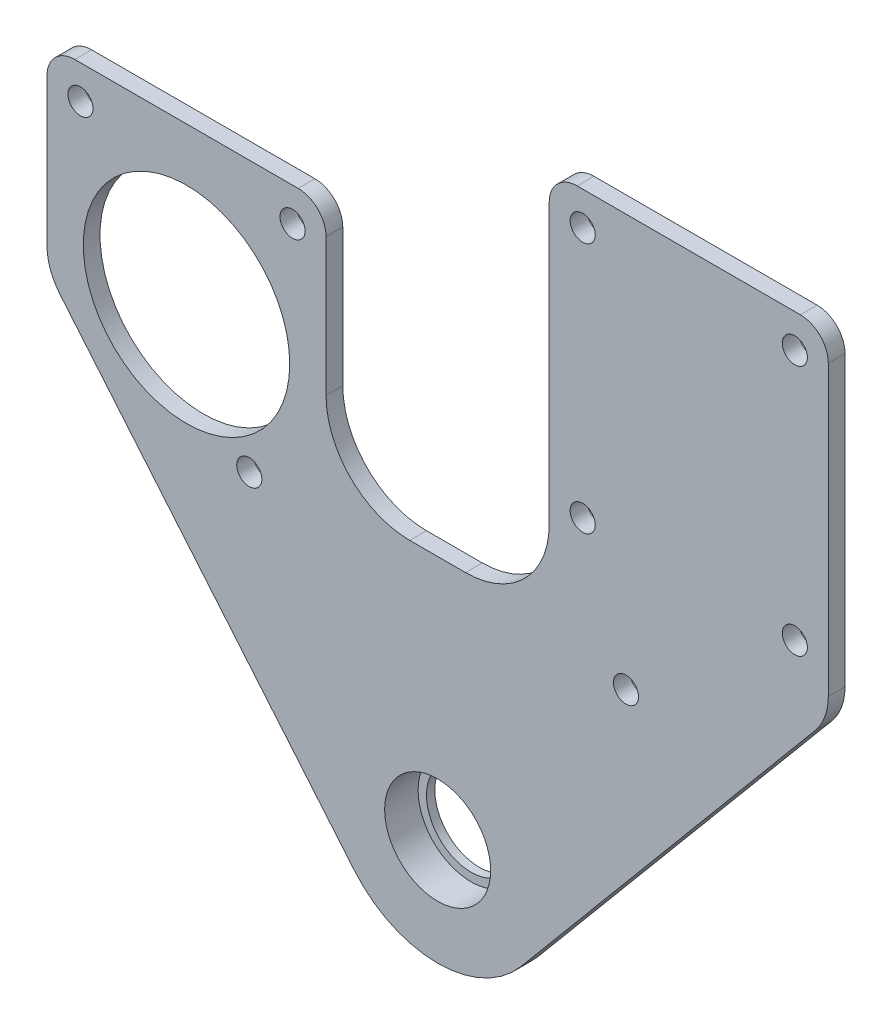
SolidWorks part; units mm, degrees
material "ABS"
ref_plane "Front Plane" through (0, 0, 0) normal (0, 0, 1) x (1, 0, 0)
ref_plane "Top Plane" through (0, 0, 0) normal (0, 1, 0) x (1, 0, 0)
ref_plane "Right Plane" through (0, 0, 0) normal (1, 0, 0) x (0, 0, -1)
sketch "Sketch1" plane through (0, 0, 0) normal (0, 0, 1) x (1, 0, 0)
  line L0 (-69.9951, 83.6231) -> (-69.9951, 57.2559)
  line L1 (-67.6634, 50.8374) -> (-14.9531, -12.1356)
  line L2 (14.9531, -12.1356) -> (67.6634, 50.8374)
  line L3 (69.9951, 57.2559) -> (69.9951, 109)
  line L4 (64.9951, 114) -> (24.9951, 114)
  line L5 (19.9951, 109) -> (19.9951, 59)
  line L6 (4.9951, 44) -> (-4.9951, 44)
  line L7 (-19.9951, 59) -> (-19.9951, 83.6231)
  line L8 (-24.9951, 88.6231) -> (-64.9951, 88.6231)
  line L9 (0, -30) -> (0, 0) construction
  line L10 (0, 0) -> (-44.9951, 53.6231) construction
  line L11 (0, 0) -> (44.9951, 53.6231) construction
  line L12 (-44.9951, 53.6231) -> (-69.9951, 53.6231) construction
  line L13 (-44.9951, 53.6231) -> (-19.9951, 53.6231) construction
  line L14 (0, 0) -> (0, 44) construction
  line L15 (44.9951, 53.6231) -> (69.9951, 53.6231) construction
  line L16 (44.9951, 53.6231) -> (19.9951, 53.6231) construction
  line L17 (-44.9951, 53.6231) -> (-44.9951, 60.6231) construction
  line L18 (19.9951, 108) -> (69.9951, 108) construction
  line L19 (0, 0) -> (-56.4396, 0) construction
  line L20 (-69.9951, 82.6231) -> (-19.9951, 82.6231) construction
  circle A0 centre (0, 0) radius 9.5
  circle A1 centre (0, 0) radius 70 construction
  arc A3 (14.9531, -12.1356) -> (-14.9531, -12.1356) centre (0, 0.3806) cw
  arc A4 (-4.9951, 44) -> (-19.9951, 59) centre (-4.9951, 59) cw
  arc A5 (19.9951, 59) -> (4.9951, 44) centre (4.9951, 59) cw
  circle A6 centre (-44.9951, 60.6231) radius 18.5
  circle A13 centre (0, 0) radius 40.8 construction
  circle A14 centre (0, 0) radius 52.5 construction
  circle A15 centre (-33.7463, 40.2173) radius 2.25
  circle A16 centre (33.7463, 40.2173) radius 2.25
  circle A17 centre (25.9951, 108) radius 2.25
  circle A18 centre (63.9951, 108) radius 2.25
  arc A19 (69.9951, 109) -> (64.9951, 114) centre (64.9951, 109) ccw
  arc A20 (24.9951, 114) -> (19.9951, 109) centre (24.9951, 109) ccw
  circle A21 centre (-63.9951, 82.6231) radius 2.25
  circle A22 centre (-25.9951, 82.6231) radius 2.25
  arc A23 (-69.9951, 83.6231) -> (-64.9951, 88.6231) centre (-64.9951, 83.6231) cw
  arc A24 (-19.9951, 83.6231) -> (-24.9951, 88.6231) centre (-24.9951, 83.6231) ccw
  circle A25 centre (25.9951, 63) radius 2.25
  circle A26 centre (63.9951, 63) radius 2.25
  arc A27 (67.6634, 50.8374) -> (69.9951, 57.2559) centre (59.9951, 57.2559) ccw
  arc A28 (-69.9951, 57.2559) -> (-67.6634, 50.8374) centre (-59.9951, 57.2559) ccw
  point P43 (-69.9951, 88.6231)
  point P46 (-43.1002, 38.0546)
  dimension "D1" = 19
  dimension "D3" = 140
  dimension "D4" = 50
  dimension "D5" = 19.5
  dimension "D7" = 15
  dimension "D8" = 15
  dimension "D10" = 37
  dimension "D11" = 50
  dimension "D12" = 81.6
  dimension "D14" = 105
  dimension "D15" = 4.5
  dimension "D16" = 4.5
  dimension "D18" = 4.5
  dimension "D19" = 4.5
  dimension "D22" = 5
  dimension "D25" = 4.5
  dimension "D26" = 4.5
  dimension "D29" = 5
  dimension "D32" = 4.5
  dimension "D33" = 4.5
  dimension "D35" = 10
  dimension "D2" = 30
  dimension "D6" = 44
  dimension "D9" = 7
  dimension "D13" = 35
  dimension "D17" = 6
  dimension "D20" = 6
  dimension "D21" = 6
  dimension "D23" = 70
  dimension "D24" = 6
  dimension "D27" = 6
  dimension "D28" = 6
  dimension "D30" = 25
  dimension "D31" = 25
  dimension "D34" = 45
extrude "Boss-Extrude1" add sketch "Sketch1" along normal blind 3
sketch "Sketch2" plane through (0, 0, 3) normal (0, 0, 1) x (1, 0, 0)
  circle A0 centre (0, 0) radius 12.5
  circle A1 centre (0, 0) radius 9.5
  circle A2 centre (0, 0) radius 12.5
  dimension "D1" = 25
sketch "Sketch3" plane through (0, 0, 0) normal (0, 0, -1) x (-1, 0, 0)
  circle A0 centre (0, 0) radius 12.5
  circle A1 centre (0, 0) radius 9.5
  dimension "D1" = 25
  dimension "D2" = 19
extrude "Boss-Extrude3" add sketch "Sketch3" along normal blind 3
sketch "Sketch4" plane through (0, 0, -3) normal (0, 0, -1) x (-1, 0, 0)
  circle A0 centre (0, 0) radius 12.5
  circle A1 centre (0, 0) radius 8
  dimension "D1" = 16
  dimension "D2" = 25
extrude "Boss-Extrude4" add sketch "Sketch4" along normal blind 1.5
fillet "Fillet1" radius 2 1 edges at (-12.5, 0, 0)
